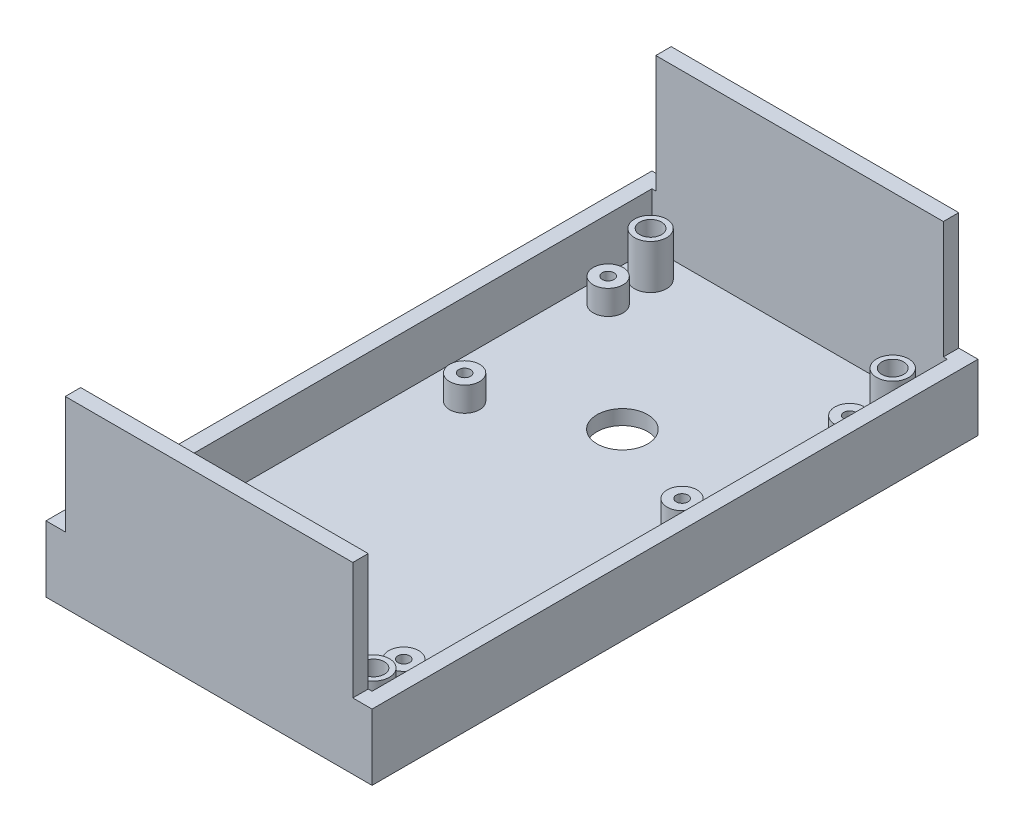
SolidWorks part; units mm, degrees
ref_plane "Front Plane" through (0, 0, 0) normal (0, 0, 1) x (1, 0, 0)
ref_plane "Top Plane" through (0, 0, 0) normal (0, 1, 0) x (1, 0, 0)
ref_plane "Right Plane" through (0, 0, 0) normal (1, 0, 0) x (0, 0, -1)
sketch "Sketch1" plane through (0, 0, 0) normal (0, 1, 0) x (1, 0, 0)
  line L1 (0, 0) -> (64.516, 0)
  line L2 (0, 0) -> (0, 119.888)
  line L3 (0, 119.888) -> (64.516, 119.888)
  line L4 (64.516, 0) -> (64.516, 119.888)
  dimension "D1" = 64.516
  dimension "D2" = 119.888
extrude "Boss-Extrude1" add sketch "Sketch1" along normal blind 13.081
sketch "Sketch2" plane through (0, 13.081, 0) normal (0, 1, 0) x (1, 0, 0)
  line L14 (3.048, 116.84) -> (3.048, 3.048)
  line L15 (3.048, 3.048) -> (61.468, 3.048)
  line L16 (61.468, 3.048) -> (61.468, 116.84)
  line L17 (61.468, 116.84) -> (3.048, 116.84)
  line L18 (3.048, 116.84) -> (3.048, 3.048)
  line L19 (3.048, 3.048) -> (61.468, 3.048)
  line L20 (61.468, 3.048) -> (61.468, 116.84)
  line L21 (61.468, 116.84) -> (3.048, 116.84)
  dimension "D1" = 3.048
extrude "Cut-Extrude1" cut sketch "Sketch2" against normal blind 10.16
sketch "Sketch3" plane through (0, 13.081, 0) normal (0, 1, 0) x (1, 0, 0)
  line L0 (61.468, 116.84) -> (3.048, 116.84) construction
  line L1 (3.81, 116.84) -> (60.706, 116.84)
  line L2 (3.81, 116.84) -> (3.81, 119.888)
  line L3 (3.81, 119.888) -> (60.706, 119.888)
  line L4 (60.706, 116.84) -> (60.706, 119.888)
  line L5 (3.048, 3.048) -> (61.468, 3.048) construction
  line L6 (3.81, 3.048) -> (60.706, 3.048)
  line L7 (3.81, 3.048) -> (3.81, 0)
  line L8 (3.81, 0) -> (60.706, 0)
  line L9 (60.706, 3.048) -> (60.706, 0)
  line L10 (0, 0) -> (64.516, 0) construction
  line L11 (64.516, 119.888) -> (0, 119.888) construction
  line L12 (32.258, 119.888) -> (32.258, 0) construction
  line L13 (0, 59.944) -> (64.516, 59.944) construction
  line L14 (0, 119.888) -> (0, 0) construction
  line L15 (64.516, 0) -> (64.516, 119.888) construction
  point P25 (32.258, 59.944)
  line M13 (61.468, 3.048) -> (3.048, 3.048)
  line M15 (0, 0) -> (64.516, 0)
  dimension "D1" = 56.896
extrude "Boss-Extrude2" add sketch "Sketch3" along normal blind 23.2156 contours L9 L7 M13 M15 | L2 L3 L4 L1 region at (32.258, 13.081, -1.524)
sketch "Sketch4" plane through (0, 2.921, 0) normal (0, 1, 0) x (1, 0, 0)
  line L0 (8.3566, 102.87) -> (56.1594, 102.87) construction
  line L1 (10.7442, 72.0852) -> (53.7718, 72.0852) construction
  line L2 (10.7442, 17.018) -> (53.7718, 17.018) construction
  line L3 (32.258, 116.84) -> (32.258, 3.048) construction
  line L4 (61.468, 116.84) -> (3.048, 116.84) construction
  line L5 (60.706, 3.048) -> (3.81, 3.048) construction
  line L6 (3.81, 116.84) -> (60.706, 116.84) construction
  line L7 (3.048, 3.048) -> (61.468, 3.048) construction
  circle A0 centre (8.3566, 102.87) radius 2.9591
  circle A1 centre (8.3566, 102.87) radius 1.1684
  circle A2 centre (56.1594, 102.87) radius 2.9591
  circle A3 centre (56.1594, 102.87) radius 1.1684
  circle A4 centre (10.7442, 72.0852) radius 2.9591
  circle A5 centre (10.7442, 72.0852) radius 1.1684
  circle A6 centre (53.7718, 72.0852) radius 1.1684
  circle A7 centre (53.7718, 72.0852) radius 2.9591
  circle A8 centre (10.7442, 17.018) radius 2.9591
  circle A9 centre (10.7442, 17.018) radius 1.1684
  circle A10 centre (53.7718, 17.018) radius 1.1684
  circle A11 centre (53.7718, 17.018) radius 2.9591
  point P24 (32.258, 102.87)
  point P25 (32.258, 72.0852)
  point P26 (32.258, 17.018)
  dimension "D1" = 2.3368
  dimension "D2" = 5.9182
  dimension "D3" = 13.97
  dimension "D4" = 13.97
  dimension "D5" = 44.7548
  dimension "D6" = 47.8028
  dimension "D7" = 43.0276
  dimension "D8" = 43.0276
extrude "Boss-Extrude3" add sketch "Sketch4" along normal blind 4.826
sketch "Sketch5" plane through (0, 2.921, 0) normal (0, 1, 0) x (1, 0, 0)
  line L1 (0, 119.888) -> (0, 0) construction
  line L2 (3.81, 119.888) -> (60.706, 119.888) construction
  circle A0 centre (31.1785, 82.8675) radius 5.0165
  dimension "D1" = 10.033
  dimension "D2" = 31.1785
  dimension "D3" = 37.0205
extrude "Cut-Extrude2" cut sketch "Sketch5" against normal through all contours A0
sketch "Sketch6" plane through (0, 2.921, 0) normal (0, 1, 0) x (1, 0, 0)
  line L0 (8.3058, 59.944) -> (3.048, 59.944) construction
  line L1 (8.3058, 111.3155) -> (56.2102, 111.3155) construction
  line L2 (8.3058, 111.3155) -> (8.3058, 8.5725) construction
  line L3 (8.3058, 8.5725) -> (56.2102, 8.5725) construction
  line L4 (56.2102, 111.3155) -> (56.2102, 8.5725) construction
  line L5 (3.048, 116.84) -> (3.048, 3.048) construction
  line L6 (32.258, 111.3155) -> (32.258, 116.84) construction
  line L7 (61.468, 116.84) -> (3.048, 116.84) construction
  line L8 (56.2102, 59.944) -> (61.468, 59.944) construction
  line L9 (61.468, 3.048) -> (61.468, 116.84) construction
  line L10 (32.258, 8.5725) -> (32.258, 3.048) construction
  line L11 (3.048, 3.048) -> (61.468, 3.048) construction
  circle A0 centre (8.3058, 111.3155) radius 2.159
  circle A1 centre (8.3058, 111.3155) radius 3.175
  circle A2 centre (56.2102, 111.3155) radius 2.159
  circle A3 centre (56.2102, 111.3155) radius 3.175
  circle A4 centre (8.3058, 8.5725) radius 3.175
  circle A5 centre (8.3058, 8.5725) radius 2.159
  circle A6 centre (56.2102, 8.5725) radius 2.159
  circle A7 centre (56.2102, 8.5725) radius 3.175
  dimension "D1" = 6.35
  dimension "D2" = 4.318
  dimension "D3" = 102.743
  dimension "D4" = 47.9044
extrude "Boss-Extrude4" add sketch "Sketch6" along normal blind 8.763
extrude "Cut-Extrude3" cut sketch "Sketch6<2>" against normal through all contours A0 | A2 | A5 | A6 region at (8.3058, 2.921, -111.3155) region at (56.2102, 2.921, -111.3155) region at (8.3058, 2.921, -8.5725) region at (56.2102, 2.921, -8.5725)
sketch "Sketch6<2>" plane through (0, 2.921, 0) normal (0, 1, 0) x (1, 0, 0) same geometry as "Sketch6"
